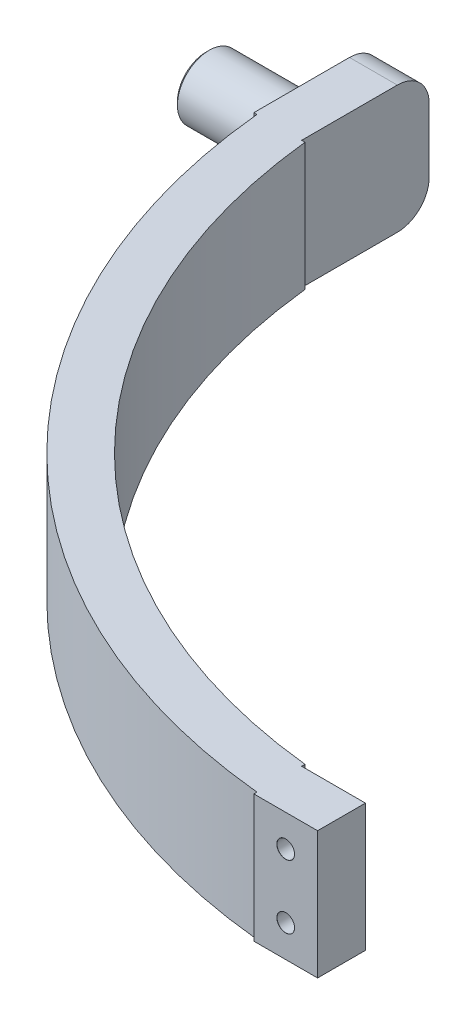
SolidWorks part; units mm, degrees
ref_plane "Front Plane" through (0, 0, 0) normal (0, 0, 1) x (1, 0, 0)
ref_plane "Top Plane" through (0, 0, 0) normal (0, 1, 0) x (1, 0, 0)
ref_plane "Right Plane" through (0, 0, 0) normal (1, 0, 0) x (0, 0, -1)
sketch "Sketch20" plane through (0, 0, 0) normal (0, 1, 0) x (1, 0, 0)
  line L0 (0, 0) -> (0, -20)
  line L1 (0, 0) -> (15, 0)
  line L7 (0, -20) -> (205, -20) construction
  line L8 (205, -20) -> (205, -225) construction
  line L11 (205, -210) -> (185, -210)
  line L12 (205, -225) -> (185, -225)
  line L13 (185, -208.9444) -> (185, -210)
  line L14 (205, -210) -> (205, -225)
  line L15 (185, -224.0221) -> (185, -225)
  line L16 (0, -20) -> (0, -40)
  line L17 (0.9779, -40) -> (0, -40)
  line L18 (15, 0) -> (15, -20)
  line L19 (15, -20) -> (15, -40)
  line L20 (16.0556, -40) -> (15, -40)
  line L21 (60.0431, -164.9569) -> (205, -20) construction
  arc A1 (16.0556, -40) -> (185, -208.9444) centre (205, -20) ccw
  arc A3 (185, -224.0221) -> (0.9779, -40) centre (205, -20) cw
  dimension "D3" = 205
  dimension "D7" = 15
  dimension "D1" = 20
  dimension "D2" = 15
  dimension "D4" = 20
  dimension "D5" = 15
  dimension "D6" = 20
extrude "Boss-Extrude4" add sketch "Sketch20" along normal blind 40 separate body
sketch "Sketch18" plane through (0, 0, 0) normal (-1, 0, 0) x (0, 0, 1)
  line L3 (0, 40) -> (40, 40) construction
  line L4 (0, 40) -> (0, 0) construction
  circle A0 centre (20, 20) radius 12.5
  point P4 (20, 40)
  point P7 (0, 20)
  dimension "D1" = 25
extrude "Boss-Extrude2" add sketch "Sketch18" along normal blind 5
sketch "Sketch19" plane through (-5, 0, 0) normal (-1, 0, 0) x (0, 0, 1)
  circle A0 centre (20, 20) radius 9.95
  dimension "D1" = 19.9
extrude "Boss-Extrude3" add sketch "Sketch19" along normal blind 30
fillet "Fillet1" radius 10 2 edges at (7.5, 0, 0) (7.5, 40, 0)
sketch "Sketch23" plane through (0, 0, 225) normal (0, 0, 1) x (1, 0, 0)
  line L0 (195, 30) -> (195, 10) construction
  line L2 (205, 40) -> (205, 0) construction
  line L3 (185, 40) -> (205, 40) construction
  point P0 (195, 30)
  point P2 (195, 10)
  point P13 (205, 20)
  point P14 (195, 20)
  point P17 (195, 40)
  dimension "D1" = 20
hole_wizard "M5 Clearance Hole1" positions "Sketch23" profile "Sketch22" hole size "M5" standard "ANSI Metric" end condition through all
sketch "Sketch22" plane through (195, 30, 225) normal (1, 0, 0) x (0, -1, 0)
  line L0 (0, 0) -> (0, 225)
  line L1 (0, 225) -> (2.75, 225)
  line L2 (2.75, 225) -> (2.75, 0.025)
  line L3 (2.75, 0.025) -> (2.775, 0)
  line L5 (2.775, 0) -> (0, 0)
  line L6 (-2.75, 0.025) -> (-2.775, 0) construction
  line L11 (0, -6.35) -> (0, 107.95) construction
  dimension "Thru Hole Dia." = 5.5
  dimension "Thru Hole Depth" = 225
  dimension "Near C'Sink Dia." = 5.55
  dimension "Near C'Sink Angle" = 90
chamfer "Chamfer1" distance 1 angle 45 1 edges at (-35, 20, 29.95)
